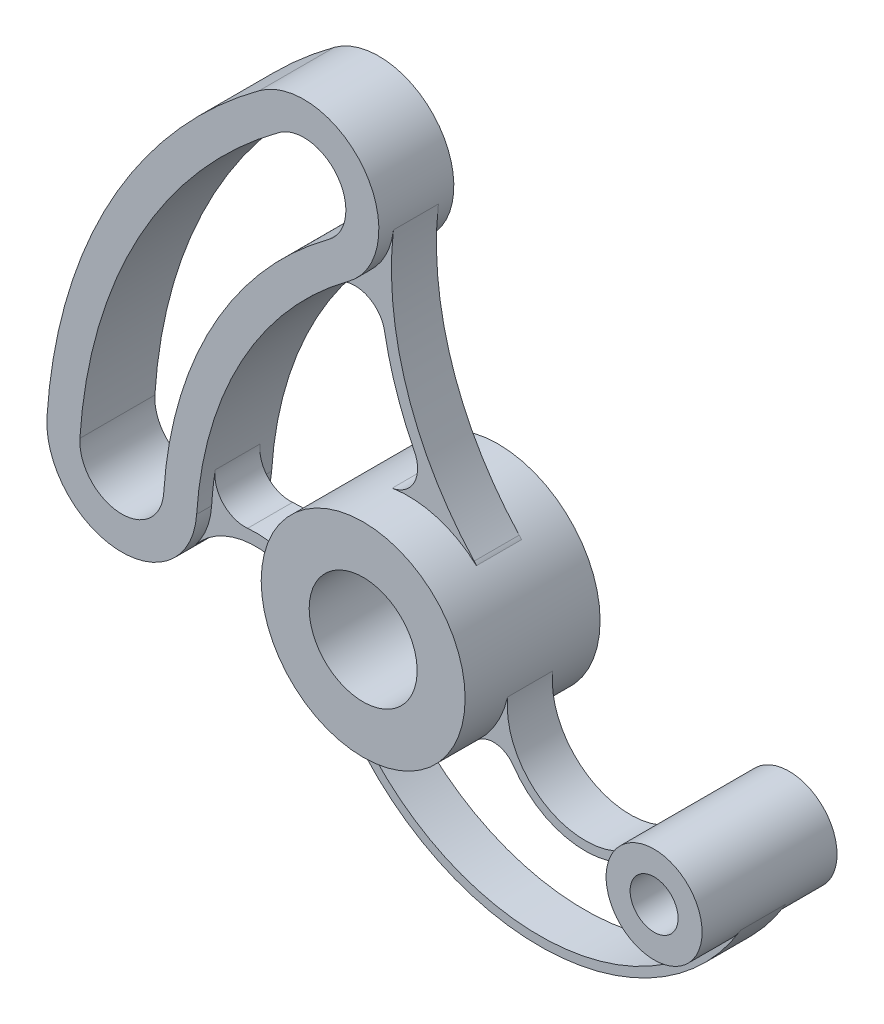
SolidWorks part; units mm, degrees
ref_plane "Front Plane" through (0, 0, 0) normal (0, 0, 1) x (1, 0, 0)
ref_plane "Top Plane" through (0, 0, 0) normal (0, 1, 0) x (1, 0, 0)
ref_plane "Right Plane" through (0, 0, 0) normal (1, 0, 0) x (0, 0, -1)
sketch "Sketch1" plane through (0, 0, 0) normal (0, 0, 1) x (1, 0, 0)
  circle A0 centre (0, 0) radius 34
  circle A1 centre (0, 0) radius 18
  dimension "D1" = 34
  dimension "D2" = 18
extrude "Boss-Extrude1" add sketch "Sketch1" along normal mid plane 45
sketch "Sketch2" plane through (0, 0, 0) normal (0, 0, 1) x (1, 0, 0)
  circle A0 centre (97, -28) radius 16
  circle A1 centre (97, -28) radius 8
  dimension "D1" = 32
  dimension "D2" = 16
  dimension "D3" = 97
  dimension "D4" = 28
extrude "Boss-Extrude2" add sketch "Sketch2" along normal mid plane 45 separate body
sketch "Sketch4" plane through (0, 0, 0) normal (0, 0, 1) x (1, 0, 0)
  line L0 (24.6461, 3.899) -> (93.436, -23.9481) construction
  arc A0 (33.206, -7.1004) -> (82.412, -21.4174) centre (59.041, -10.0245) ccw
  circle A1 centre (97, -28) radius 16 construction
  arc A2 (30.471, -14.9996) -> (81.074, -28.8805) centre (59.041, -10.0245) ccw
  circle A3 centre (59.041, -10.0245) radius 29 construction
  circle A4 centre (59.041, -10.0245) radius 26 construction
  arc A5 (33.206, -7.1004) -> (30.471, -14.9996) centre (4.3204, -1.5222) cw
  arc A6 (82.412, -21.4174) -> (81.074, -28.8805) centre (100.2765, -28.4717) ccw
  point P10 (59.041, -10.0245)
  dimension "D1" = 26
  dimension "D2" = 3
extrude "Boss-Extrude4" add sketch "Sketch4" along normal mid plane 15
sketch "Sketch5" plane through (0, 0, 0) normal (0, 0, 1) x (1, 0, 0)
  arc A0 (-34.0315, -0.7923) -> (110.8813, -35.9616) centre (43.828, 3.8864) ccw
  circle A1 centre (0, 0) radius 34 construction
  circle A2 centre (97, -28) radius 16 construction
  arc A3 (-27.207, -20.1764) -> (102.4516, -42.8926) centre (43.828, 3.8864) ccw
  arc A4 (-27.207, -20.1764) -> (-34.0315, -0.7923) centre (3.2779, 1.4497) cw
  arc A5 (110.8813, -35.9616) -> (102.4516, -42.8926) centre (97.0673, -27.7523) cw
  arc A7 (-31.0369, -0.6123) -> (108.3023, -34.429) centre (43.828, 3.8864) ccw construction
  dimension "D1" = 78
  dimension "D2" = 3
extrude "Boss-Extrude5" add sketch "Sketch5" along normal mid plane 15
sketch "Sketch8" plane through (0, 0, 0) normal (0, 0, 1) x (1, 0, 0)
  line L4 (-115.4709, 0) -> (-115.5154, 0)
  arc A1 (-4.9242, 108.3126) -> (23.2756, 24.8364) centre (98.4283, 96.7258) ccw
  arc A2 (-31.9195, -14.0754) -> (-71.0031, -15.6845) centre (-50.7566, -31.9964) ccw
  arc A4 (-44.5997, 131.2235) -> (-115.4191, 1.6093) centre (59.218, -9.6555) ccw
  arc A5 (-14.9375, 90.9723) -> (-65.5228, -1.6093) centre (59.218, -9.6555) ccw
  arc A6 (-21.4632, 99.8276) -> (-76.5, -0.9012) centre (59.218, -9.6555) ccw
  arc A7 (-21.4632, 99.8276) -> (-38.074, 122.3682) centre (-29.7686, 111.0979) ccw
  arc A8 (-115.4191, 1.6093) -> (-65.5228, -1.6093) centre (-90.4709, 0) ccw
  arc A9 (-14.9375, 90.9723) -> (-44.5997, 131.2235) centre (-29.7686, 111.0979) ccw
  arc A10 (-38.074, 122.3682) -> (-104.4419, 0.9012) centre (59.218, -9.6555) ccw
  arc A11 (-104.4419, 0.9012) -> (-76.5, -0.9012) centre (-90.4709, 0) ccw
  circle A12 centre (0, 0) radius 34 construction
  arc A13 (-9.5711, 96.3649) -> (12.3046, 31.559) centre (98.4283, 96.7258) ccw
  arc A15 (12.3046, 31.559) -> (23.2756, 24.8364) centre (-6.0595, -10.7241) cw
  circle A16 centre (98.4283, 96.7258) radius 108 construction
  circle A17 centre (98.4283, 96.7258) radius 104 construction
  arc A18 (-33.3244, -7.5808) -> (-66.2851, -6.328) centre (-50.7566, -31.9964) ccw
  arc A19 (-71.0031, -15.6845) -> (-66.2851, -6.328) centre (-90.4709, 0) ccw
  arc A20 (-33.8671, -3.0031) -> (110.7218, -36.2287) centre (43.828, 3.8864) ccw construction
  circle A21 centre (-50.7566, -31.9964) radius 30 construction
  arc A22 (-31.9195, -14.0754) -> (-33.3244, -7.5808) centre (24.6782, 1.5677) cw
  circle A23 centre (-50.7566, -31.9964) radius 26 construction
  arc A25 (-9.5711, 96.3649) -> (-4.9242, 108.3126) centre (-29.7686, 111.0979) ccw
  arc A26 (-115.4191, 1.6093) -> (-65.4709, 0) centre (-90.4709, 0) ccw construction
  arc A27 (-104.4419, 0.9012) -> (-76.4709, 0) centre (-90.4709, 0) ccw construction
  arc A28 (-44.5997, 131.2235) -> (-115.5154, 0) centre (59.218, -9.6555) ccw construction
  arc A29 (-38.074, 122.3682) -> (-104.5322, -0.6069) centre (59.218, -9.6555) ccw construction
  point P40 (-71.0031, -15.6845)
  point P41 (-66.2851, -6.328)
  point P45 (-33.3244, -7.5808)
  point P46 (-31.9195, -14.0754)
  dimension "D5" = 4
  dimension "D3" = 50
extrude "Boss-Extrude13" add sketch "Sketch8" along normal mid plane 25 separate body contours A5 A9 A4 A8 A11 A10 A7 A6 region at (-8.2906, 102.7444, 0)
extrude "Boss-Extrude14" add sketch "Sketch8<9>" along normal mid plane 15 contours A13 A15 A1 A25 | A2 A19 A18 A22
sketch "Sketch8<9>" plane through (0, 0, 0) normal (0, 0, 1) x (1, 0, 0) same geometry as "Sketch8"
fillet "Fillet14" radius 10 6 edges at (-9.5711, 96.3649, 0) (12.1593, 31.7514, 0) (23.2756, 24.8364, 0) (-32.1262, -13.8605, 0) (-33.3244, -7.5808, 0) (-66.2851, -6.328, 0)
fillet "Fillet16" radius 8 2 edges at (102.2836, -43.1024, 0) (-27.0732, -20.568, 0)
fillet "Fillet17" radius 8 2 edges at (81.0273, -28.9349, 0) (30.4819, -15.0617, 0)
